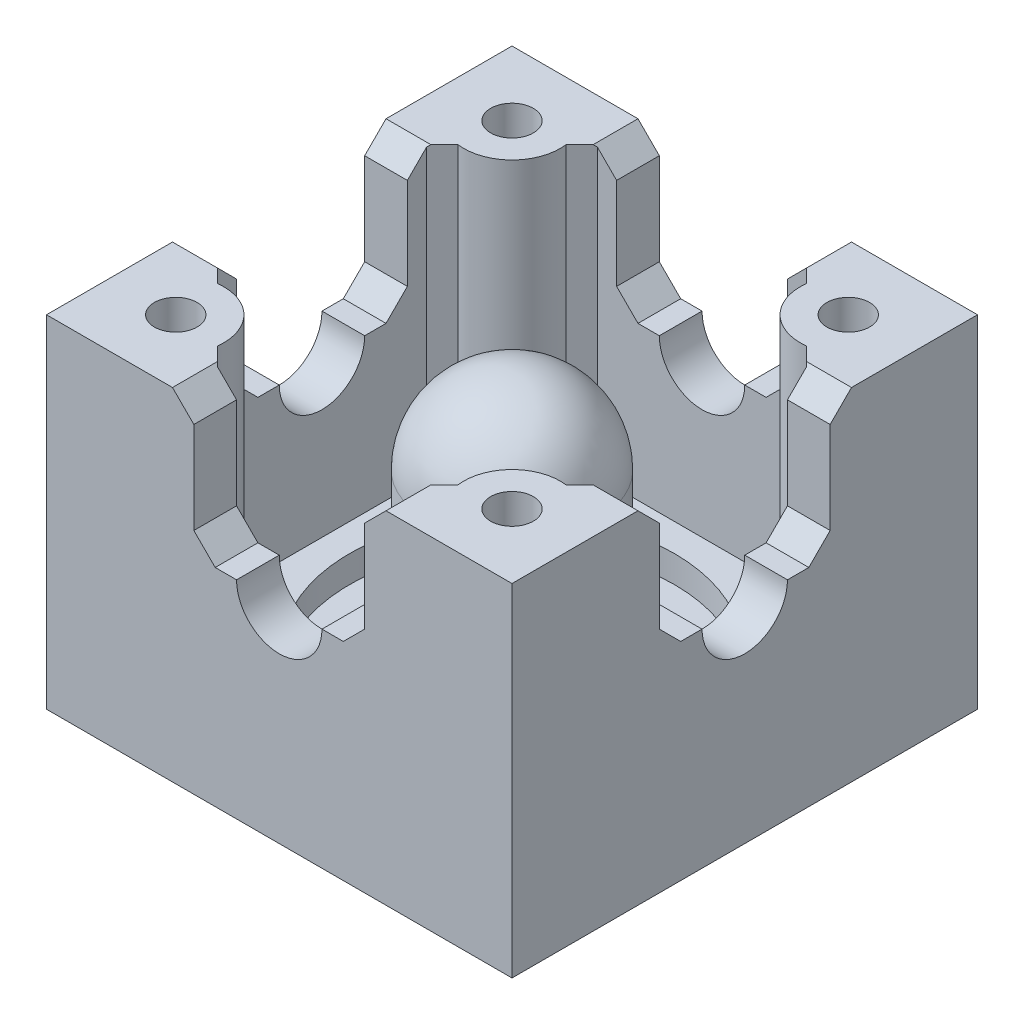
SolidWorks part; units mm, degrees
ref_plane "Front Plane" through (0, 0, 0) normal (0, 0, 1) x (1, 0, 0)
ref_plane "Top Plane" through (0, 0, 0) normal (0, 1, 0) x (1, 0, 0)
ref_plane "Right Plane" through (0, 0, 0) normal (1, 0, 0) x (0, 0, -1)
sketch "Sketch1" plane through (0, 0, 0) normal (0, 1, 0) x (1, 0, 0)
  line L1 (0, 0) -> (13.843, 0)
  line L2 (0, 0) -> (0, 13.843)
  line L3 (0, 13.843) -> (13.843, 13.843)
  line L4 (13.843, 0) -> (13.843, 13.843)
  dimension "D1" = 13.843
  dimension "D2" = 13.843
extrude "main body extrude" add sketch "Sketch1" along normal blind 10.16
sketch "Sketch4" plane through (0, 10.16, 0) normal (0, 1, 0) x (1, 0, 0)
  line L0 (0, 13.843) -> (13.843, 0) construction
  line L1 (13.843, 0) -> (13.843, 13.843) construction
  line L2 (1.27, 10.033) -> (3.81, 12.573)
  line L7 (13.843, 13.843) -> (0, 13.843) construction
  line L8 (3.81, 1.27) -> (10.033, 1.27)
  line L9 (10.033, 12.573) -> (12.573, 10.033)
  line L10 (0, 0) -> (13.843, 0) construction
  line L15 (1.27, 3.81) -> (1.27, 10.033)
  line L16 (3.81, 12.573) -> (10.033, 12.573)
  line L17 (12.573, 3.81) -> (12.573, 10.033)
  line L18 (1.27, 1.27) -> (12.573, 12.573) construction
  line L19 (1.27, 12.573) -> (12.573, 1.27) construction
  line L20 (10.033, 1.27) -> (12.573, 3.81)
  line L21 (1.27, 3.81) -> (3.81, 1.27)
  circle A0 centre (1.9215, 11.9215) radius 0.635
  circle A1 centre (11.9215, 11.9215) radius 0.635
  circle A2 centre (11.9215, 1.9215) radius 0.635
  circle A3 centre (1.9215, 1.9215) radius 0.635
  circle A4 centre (1.9215, 11.9215) radius 1.435
  circle A5 centre (11.9215, 11.9215) radius 1.435
  circle A6 centre (11.9215, 1.9215) radius 1.435
  circle A7 centre (1.9215, 1.9215) radius 1.435
  point P5 (6.9215, 6.9215)
  point P6 (6.9215, 6.9215)
  point P27 (6.9215, 6.9215)
  point P28 (6.9215, 6.9215)
  point P44 (6.9215, 6.9215)
  dimension "D3" = 1.27
  dimension "D6" = 0.8
  dimension "D1" = 1.27
  dimension "D2" = 1.27
  dimension "D5" = 10
  dimension "D4" = 4
  dimension "D7" = 4
extrude "main body cut" cut sketch "Sketch4" against normal offset from surface (9.36 mm away) 0.8 contours L8 region at (6.9215, 10.16, -6.9215) up to face at (6.9215, 0, -6.9215)
sketch "Sketch21" plane through (0, 10.16, 0) normal (0, 1, 0) x (1, 0, 0)
  line L0 (0, 13.843) -> (13.843, 0) construction
  circle A0 centre (1.9215, 11.9215) radius 0.635
  circle A1 centre (11.9215, 11.9215) radius 0.635
  circle A2 centre (11.9215, 1.9215) radius 0.635
  circle A3 centre (1.9215, 1.9215) radius 0.635
  point P7 (6.9215, 6.9215)
  point P17 (6.9215, 6.9215)
  dimension "D2" = 1.27
  dimension "D1" = 4
extrude "screw holes cut" cut sketch "Sketch21" against normal through all
sketch "Sketch5" plane through (0, 0, 0) normal (0, 0, 1) x (1, 0, 0)
  line L0 (6.9215, 12.7116) -> (6.9215, 6.1595) construction
  line L1 (8.1915, 12.7116) -> (8.1915, 6.1595)
  line L2 (0, 10.16) -> (13.843, 10.16) construction
  line L3 (5.6515, 12.7116) -> (5.6515, 6.1595)
  line L4 (6.9215, 6.1595) -> (6.9215, 2.6781) construction
  line L5 (4.3815, 12.7116) -> (9.4615, 12.7116)
  line L6 (4.3815, 12.7116) -> (4.3815, 6.1595)
  line L7 (4.3815, 6.1595) -> (9.4615, 6.1595)
  line L8 (9.4615, 12.7116) -> (9.4615, 6.1595)
  line L9 (4.3815, 12.7116) -> (9.4615, 6.1595) construction
  line L10 (4.3815, 6.1595) -> (9.4615, 12.7116) construction
  line L19 (11.811, 5.207) -> (10.541, 5.207)
  line L20 (2.032, 8.509) -> (3.302, 8.509)
  line L21 (2.032, 8.509) -> (2.032, 5.207)
  line L22 (2.032, 5.207) -> (3.302, 5.207)
  line L23 (3.302, 8.509) -> (3.302, 5.207)
  line L24 (10.541, 8.509) -> (10.541, 5.207)
  line L25 (11.811, 8.509) -> (10.541, 8.509)
  line L26 (11.811, 8.509) -> (11.811, 5.207)
  arc A1 (8.1915, 12.7116) -> (5.6515, 12.7116) centre (6.9215, 12.7116) ccw
  arc A2 (5.6515, 6.1595) -> (8.1915, 6.1595) centre (6.9215, 6.1595) ccw
  circle A3 centre (6.9215, 6.1595) radius 1.27 construction
  point P2 (6.9215, 10.16)
  point P3 (6.9215, 9.4356)
  point P14 (6.9215, 9.4356)
  line M8 (13.843, 10.16) -> (0, 10.16)
  dimension "D1" = 2.54
  dimension "D2" = 4.0005
  dimension "D3" = 5.08
  dimension "D4" = 1.27
  dimension "D5" = 3.302
  dimension "D6" = 7.239
  dimension "D7" = 1.651
extrude "x axis slot" cut sketch "Sketch5" against normal through all contours L6 L7 L3 M8 | L3 L7 L1 M8 | L8 L1 L7 M8 | L7 A2 region at (8.8265, 8.1598, 0) region at (6.9215, 8.1598, 0) region at (6.9215, 5.6205, 0) region at (5.0165, 8.1598, 0)
sketch "Sketch6" plane through (13.843, 0, 0) normal (1, 0, 0) x (0, 0, -1)
  line L0 (0, 10.16) -> (13.843, 10.16) construction
  line L1 (6.9215, 6.1595) -> (6.9215, 12.6452) construction
  line L2 (5.6515, 6.1595) -> (5.6515, 12.6452)
  line L3 (8.1915, 6.1595) -> (8.1915, 12.6452)
  line L4 (6.9215, 6.1595) -> (6.9215, 2.9038) construction
  line L5 (4.3815, 12.6452) -> (9.4615, 12.6452)
  line L6 (4.3815, 12.6452) -> (4.3815, 6.1595)
  line L7 (4.3815, 6.1595) -> (9.4615, 6.1595)
  line L8 (9.4615, 12.6452) -> (9.4615, 6.1595)
  line L9 (4.3815, 12.6452) -> (9.4615, 6.1595) construction
  line L10 (4.3815, 6.1595) -> (9.4615, 12.6452) construction
  circle A0 centre (6.9215, 6.1595) radius 1.27 construction
  arc A1 (5.6515, 6.1595) -> (8.1915, 6.1595) centre (6.9215, 6.1595) ccw
  arc A2 (8.1915, 12.6452) -> (5.6515, 12.6452) centre (6.9215, 12.6452) ccw
  point P6 (6.9215, 10.16)
  point P7 (6.9215, 9.4024)
  point P13 (6.9215, 7.4295)
  point P15 (6.9215, 9.4024)
  line M8 (13.843, 10.16) -> (0, 10.16)
  dimension "D1" = 2.54
  dimension "D2" = 4.0005
  dimension "D3" = 5.08
extrude "y axis slot" cut sketch "Sketch6" against normal through all contours L6 L7 L2 M8 | L2 L7 L3 M8 | L7 A1 | L8 L3 L7 M8 region at (13.843, 8.1598, -5.0165) region at (13.843, 8.1598, -6.9215) region at (13.843, 5.6205, -6.9215) region at (13.843, 8.1598, -8.8265)
sketch "Sketch11" plane through (0, 0.8, 0) normal (0, 1, 0) x (1, 0, 0)
  line L0 (1.27, 12.573) -> (12.573, 1.27) construction
  line L1 (12.573, 12.573) -> (1.27, 1.27) construction
  line L3 (1.27, 12.573) -> (12.573, 12.573)
  line L4 (1.27, 12.573) -> (1.27, 1.27)
  line L5 (1.27, 1.27) -> (12.573, 1.27)
  line L6 (12.573, 12.573) -> (12.573, 1.27)
  line L9 (3.81, 12.573) -> (4.3815, 12.573) construction
  line L10 (1.27, 9.4615) -> (1.27, 10.033) construction
  line L12 (3.81, 1.27) -> (4.3815, 1.27) construction
  circle A0 centre (6.9215, 6.9215) radius 4.826
  circle A1 centre (1.9215, 11.9215) radius 0.635
  circle A2 centre (11.9215, 11.9215) radius 0.635
  circle A3 centre (11.9215, 1.9215) radius 0.635
  circle A4 centre (1.9215, 1.9215) radius 0.635
  dimension "D1" = 9.652
extrude "spring retainer extrude" add sketch "Sketch11" along normal blind 0.8
sketch "Sketch12" plane through (0, 0.8, 0) normal (0, 1, 0) x (1, 0, 0)
  line L0 (0, 13.843) -> (13.843, 0) construction
  circle A0 centre (6.9215, 6.9215) radius 2.54
  dimension "D1" = 5.08
extrude "Stick support" add sketch "Sketch12" along normal up to vertex (5.3595 mm away) up to point (5.6515, 6.1595, -1.27)
sketch "Sketch20" plane through (0, 6.1595, 0) normal (0, 1, 0) x (1, 0, 0)
  circle A0 centre (6.9215, 6.9215) radius 2.54
  circle A1 centre (6.9215, 6.9215) radius 2.54 construction
extrude "Boss-Extrude9" add sketch "Sketch20" along normal blind 2.54
fillet "Fillet4" radius 2.54 1 edges at (6.9215, 8.6995, -4.3815)
sketch "Sketch16" [suppressed] plane through (0, 10.16, 0) normal (0, 1, 0) x (1, 0, 0)
  line L0 (1.2, 10.103) -> (3.74, 12.643)
  line L1 (1.2, 12.643) -> (1.2, 1.2) construction
  line L2 (12.643, 12.643) -> (1.2, 12.643) construction
  line L3 (1.2, 10.103) -> (1.2, 12.643)
  line L4 (1.2, 12.643) -> (3.74, 12.643)
  line L5 (0, 13.843) -> (13.843, 0) construction
  line L6 (10.103, 12.643) -> (12.643, 10.103)
  line L7 (12.643, 12.643) -> (12.643, 10.103)
  line L8 (10.103, 12.643) -> (12.643, 12.643)
  line L9 (12.643, 3.74) -> (10.103, 1.2)
  line L10 (12.643, 1.2) -> (10.103, 1.2)
  line L11 (12.643, 3.74) -> (12.643, 1.2)
  line L12 (3.74, 1.2) -> (1.2, 3.74)
  line L13 (1.2, 1.2) -> (1.2, 3.74)
  line L14 (3.74, 1.2) -> (1.2, 1.2)
  point P12 (6.9215, 6.9215)
  point P25 (6.9215, 6.9215)
  dimension "D1" = 2.54
  dimension "D2" = 2.54
  dimension "D3" = 4
extrude "screw extrude 1" [suppressed] add sketch "Sketch16" against normal up to surface (8.56 mm away) up to face at (6.9215, 1.6, -2.0955)
sketch "Sketch15" [suppressed] plane through (0, 10.16, 0) normal (0, 1, 0) x (1, 0, 0)
  line L0 (0, 13.843) -> (13.843, 0) construction
  circle A0 centre (1.9215, 11.9215) radius 0.635
  circle A1 centre (11.9215, 11.9215) radius 0.635
  circle A2 centre (11.9215, 1.9215) radius 0.635
  circle A3 centre (1.9215, 1.9215) radius 0.635
  point P4 (6.9215, 6.9215)
  point P16 (6.9215, 6.9215)
  dimension "D1" = 1.27
  dimension "D3" = 10
  dimension "D2" = 4
extrude "screw cut 2" [suppressed] cut sketch "Sketch15" against normal through all
sketch "Sketch17" [suppressed] plane through (0, 10.16, 0) normal (0, 1, 0) x (1, 0, 0)
  line L0 (0, 13.843) -> (13.843, 0) construction
  circle A0 centre (1.9215, 11.9215) radius 1.143
  circle A1 centre (11.9215, 11.9215) radius 1.143
  circle A2 centre (11.9215, 1.9215) radius 1.143
  circle A3 centre (1.9215, 1.9215) radius 1.143
  circle A4 centre (1.9215, 11.9215) radius 0.635 construction
  circle A5 centre (1.9215, 11.9215) radius 0.635
  circle A6 centre (11.9215, 11.9215) radius 0.635
  circle A7 centre (11.9215, 1.9215) radius 0.635
  circle A8 centre (1.9215, 1.9215) radius 0.635
  point P7 (6.9215, 6.9215)
  point P17 (6.9215, 6.9215)
  point P27 (6.9215, 6.9215)
  dimension "D2" = 0.508
  dimension "D1" = 4
  dimension "D3" = 4
extrude "screw extrude 2" [suppressed] add sketch "Sketch17" against normal up to surface (8.56 mm away) up to face at (6.9215, 1.6, -2.0955)
sketch "Sketch9" plane through (0, 0, 0) normal (0, -1, 0) x (1, 0, 0)
  line L0 (6.9215, 0) -> (6.9215, -13.843) construction
  line L1 (0, 0) -> (13.843, 0) construction
  line L2 (13.843, -13.843) -> (0, -13.843) construction
  line L3 (0, -6.9215) -> (13.843, -6.9215) construction
  line L4 (0, -13.843) -> (0, 0) construction
  line L5 (13.843, 0) -> (13.843, -13.843) construction
  circle A0 centre (6.9215, -1.8415) radius 0.625
  circle A1 centre (6.9215, -12.0015) radius 0.625
  dimension "D1" = 1.25
  dimension "D2" = 10.16
extrude "mounting holes 1 cut " [suppressed] cut sketch "Sketch9" against normal blind 2.54
chamfer "Chamfer1" distance 0.635 angle 45 16 edges at (0.635, 10.16, -9.4615) (0.635, 6.1595, -9.4615) (0.635, 6.1595, -4.3815) (0.635, 10.16, -4.3815) (9.4615, 10.16, -0.635) (9.4615, 6.1595, -0.635) (4.3815, 6.1595, -0.635) (4.3815, 10.16, -0.635) (13.208, 10.16, -4.3815) (13.208, 6.1595, -4.3815) (13.208, 6.1595, -9.4615) (13.208, 10.16, -9.4615) (9.4615, 10.16, -13.208) (9.4615, 6.1595, -13.208) (4.3815, 6.1595, -13.208) (4.3815, 10.16, -13.208)
